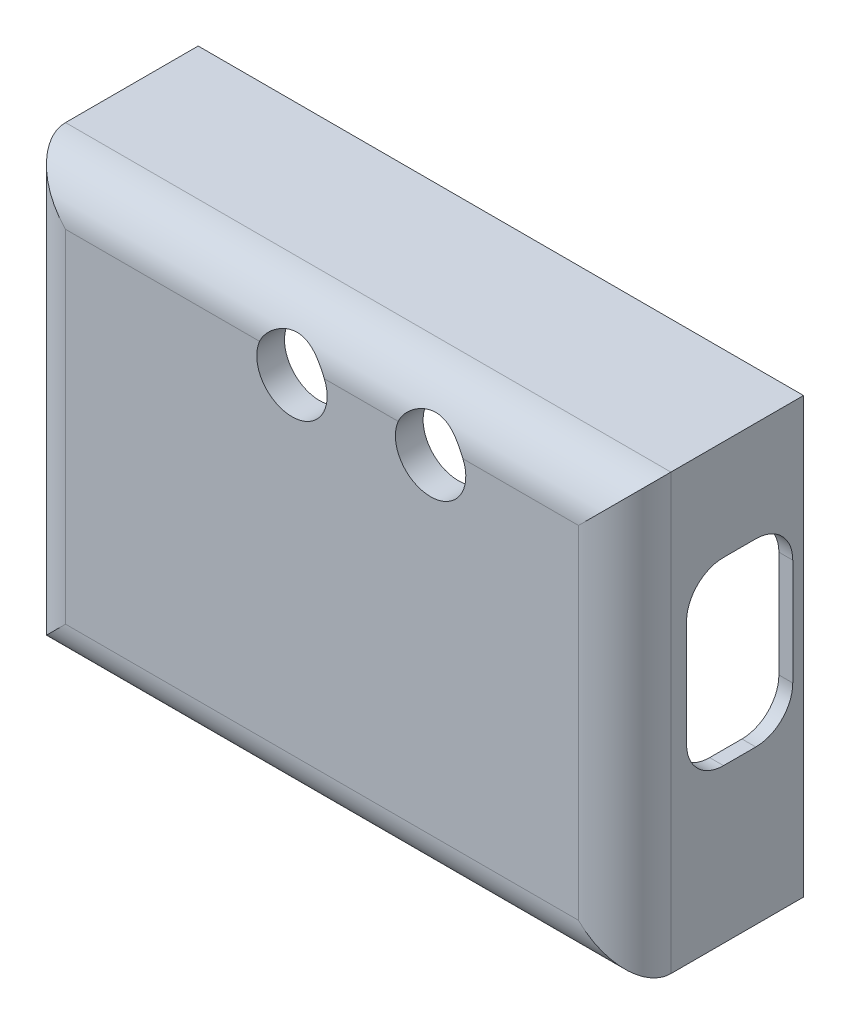
SolidWorks part; units mm, degrees
ref_plane "Front Plane" through (0, 0, 0) normal (0, 0, 1) x (1, 0, 0)
ref_plane "Top Plane" through (0, 0, 0) normal (0, 1, 0) x (1, 0, 0)
ref_plane "Right Plane" through (0, 0, 0) normal (1, 0, 0) x (0, 0, -1)
sketch "Sketch1" plane through (0, 0, 0) normal (0, 0, 1) x (1, 0, 0)
  line L0 (-70.5, -113.5) -> (-70.5, -69.5)
  line L1 (-70.5, -69.5) -> (-133, -69.5)
  line L2 (-133, -69.5) -> (-133, -113.5)
  line L3 (-133, -113.5) -> (-70.5, -113.5)
  line L4 (-71, -113) -> (-71, -70)
  line L5 (-71, -70) -> (-132.5, -70)
  line L6 (-132.5, -70) -> (-132.5, -113)
  line L7 (-132.5, -113) -> (-71, -113)
  line L8 (-71, -113) -> (-71, -70)
  line L9 (-71, -70) -> (-132.5, -70)
  line L10 (-132.5, -70) -> (-132.5, -113)
  line L11 (-132.5, -113) -> (-71, -113)
  line L12 (-69, -115) -> (-69, -68)
  line L13 (-69, -68) -> (-134.5, -68)
  line L14 (-134.5, -68) -> (-134.5, -115)
  line L15 (-134.5, -115) -> (-69, -115)
  dimension "D1" = 0
  dimension "D2" = 0.5
  dimension "D3" = 2
extrude "Boss-Extrude1" add sketch "Sketch1" along normal blind 13.97 and the other way blind 2.3813 contours L14 L15 L12 L13 L3 L2 L1 L0 region at (-101.75, -114.1938, 0)
sketch "Sketch2" plane through (0, 0, 13.97) normal (0, 0, 1) x (1, 0, 0)
  line L1 (-134.5, -68) -> (-129.42, -68)
  line L2 (-134.5, -68) -> (-134.5, -73.08)
  line L3 (-134.5, -73.08) -> (-129.42, -73.08)
  line L4 (-134.5, -68) -> (-134.5, -115)
  line L5 (-134.5, -115) -> (-69, -115)
  line L6 (-69, -115) -> (-69, -68)
  line L7 (-69, -68) -> (-134.5, -68)
  line L8 (-134.5, -68) -> (-134.5, -115)
  line L9 (-134.5, -115) -> (-69, -115)
  line L10 (-69, -115) -> (-69, -68)
  line L11 (-69, -68) -> (-134.5, -68)
  line L12 (-129.42, -68) -> (-129.42, -73.08)
  line L13 (-69, -68) -> (-74.08, -68)
  line L14 (-69, -68) -> (-69, -73.08)
  line L15 (-69, -73.08) -> (-74.08, -73.08)
  line L16 (-74.08, -68) -> (-74.08, -73.08)
  line L17 (-69, -115) -> (-74.08, -115)
  line L18 (-69, -115) -> (-69, -109.92)
  line L19 (-69, -109.92) -> (-74.08, -109.92)
  line L20 (-74.08, -115) -> (-74.08, -109.92)
  line L21 (-134.5, -115) -> (-129.42, -115)
  line L22 (-134.5, -115) -> (-134.5, -109.92)
  line L23 (-134.5, -109.92) -> (-129.42, -109.92)
  line L24 (-129.42, -115) -> (-129.42, -109.92)
  line M21 (-70.5, -113.5) -> (-133, -113.5)
  line M22 (-133, -113.5) -> (-133, -69.5)
  line M23 (-133, -69.5) -> (-70.5, -69.5)
  line M24 (-70.5, -69.5) -> (-70.5, -113.5)
  dimension "D2" = 5.08
  dimension "D1" = 0
extrude "Boss-Extrude2" add sketch "Sketch2" against normal up to surface (13.97 mm away) contours L12 L3 M23 M22 | L24 L23 M21 M22 | L20 L19 M21 M24 | L16 L15 M23 M24 region at (-131.21, -71.29, 13.97) region at (-72.29, -71.29, 13.97) region at (-131.21, -111.71, 13.97) region at (-72.29, -111.71, 13.97)
sketch "Sketch3" plane through (0, 0, 13.97) normal (0, 0, 1) x (1, 0, 0)
  line L4 (-134.5, -68) -> (-134.5, -115)
  line L5 (-134.5, -115) -> (-69, -115)
  line L6 (-69, -115) -> (-69, -68)
  line L7 (-69, -68) -> (-134.5, -68)
  line L8 (-134.5, -68) -> (-134.5, -115)
  line L9 (-134.5, -115) -> (-69, -115)
  line L10 (-69, -115) -> (-69, -68)
  line L11 (-69, -68) -> (-134.5, -68)
  circle A0 centre (-105, -74.5) radius 3.81
  circle A1 centre (-90, -74.5) radius 3.81
  dimension "D2" = 7.62
  dimension "D1" = 0
extrude "Boss-Extrude3" add sketch "Sketch3" along normal blind 3
fillet "Fillet1" radius 5 4 edges at (-101.75, -115, 16.97) (-134.5, -91.5, 16.97) (-101.75, -68, 16.97) (-69, -91.5, 16.97)
sketch "Sketch4" plane through (-69, 0, 0) normal (1, 0, 0) x (0, 0, -1)
  line L1 (-2.7849, -78.847) -> (-6.2762, -78.847)
  line L2 (1.2151, -82.847) -> (1.2151, -94.3513)
  line L3 (-2.7849, -98.3513) -> (-6.2762, -98.3513)
  line L4 (2.3813, -68) -> (-11.97, -68)
  line L5 (-11.97, -68) -> (-11.97, -115)
  line L6 (-11.97, -115) -> (2.3813, -115)
  line L7 (2.3813, -115) -> (2.3813, -68)
  line L8 (2.3813, -68) -> (-11.97, -68)
  line L9 (-11.97, -68) -> (-11.97, -115)
  line L10 (-11.97, -115) -> (2.3813, -115)
  line L11 (2.3813, -115) -> (2.3813, -68)
  line L12 (-10.2762, -82.847) -> (-10.2762, -94.3513)
  arc A0 (1.2151, -82.847) -> (-2.7849, -78.847) centre (-2.7849, -82.847) ccw
  arc A1 (1.2151, -94.3513) -> (-2.7849, -98.3513) centre (-2.7849, -94.3513) cw
  arc A2 (-6.2762, -98.3513) -> (-10.2762, -94.3513) centre (-6.2762, -94.3513) cw
  arc A3 (-10.2762, -82.847) -> (-6.2762, -78.847) centre (-6.2762, -82.847) cw
  dimension "D2" = 4
  dimension "D1" = 0
extrude "Cut-Extrude1" cut sketch "Sketch4" against normal up to surface (1.5 mm away) contours A3 L12 A2 L3 A1 L2 A0 L1 region at (-69, -88.5992, 4.5305) up to face at (-70.5, -91.5, 2.8972)
